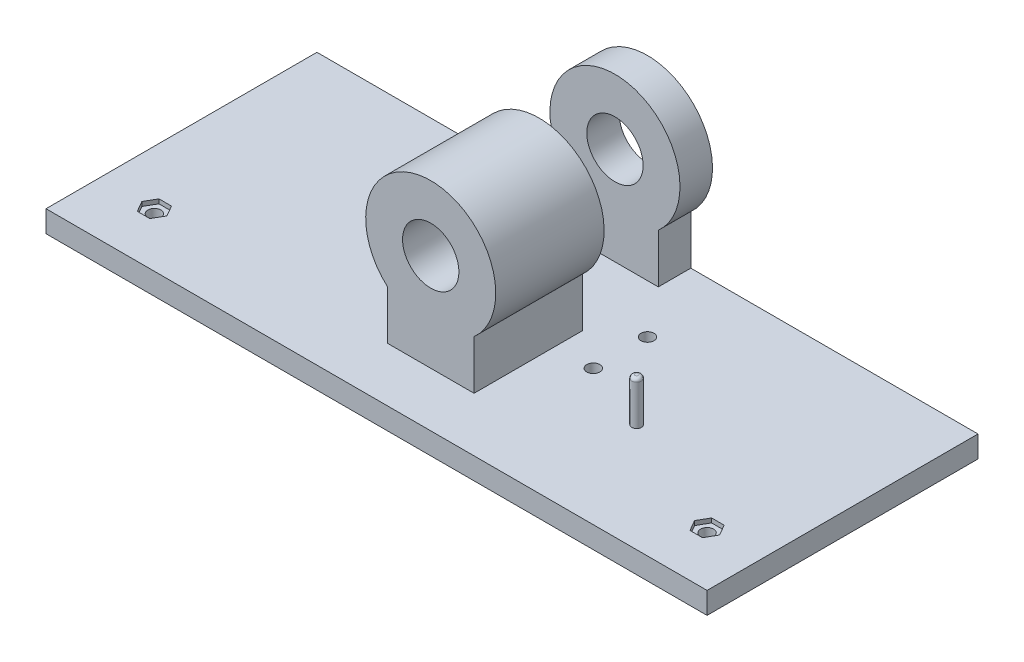
SolidWorks part; units mm, degrees
ref_plane "Front Plane" through (0, 0, 0) normal (0, 0, 1) x (1, 0, 0)
ref_plane "Top Plane" through (0, 0, 0) normal (0, 1, 0) x (1, 0, 0)
ref_plane "Right Plane" through (0, 0, 0) normal (1, 0, 0) x (0, 0, -1)
sketch "Sketch1" plane through (0, 0, 0) normal (0, 1, 0) x (1, 0, 0)
  line L0 (152.5, 125) -> (152.5, 0) construction
  line L1 (0, 0) -> (305, 0)
  line L2 (0, 0) -> (0, 125)
  line L3 (0, 125) -> (305, 125)
  line L4 (305, 0) -> (305, 125)
  line L5 (25, 100) -> (280, 100) construction
  line L6 (280, 25) -> (280, 100) construction
  line L7 (25, 25) -> (280, 25) construction
  line L8 (25, 25) -> (25, 100) construction
  line L9 (152.5, 62.5) -> (25, 62.5) construction
  line L10 (30.7735, 100) -> (27.8868, 105) construction
  line L11 (27.8868, 105) -> (22.1132, 105) construction
  line L12 (22.1132, 105) -> (19.2265, 100) construction
  line L13 (19.2265, 100) -> (22.1132, 95) construction
  line L14 (22.1132, 95) -> (27.8868, 95) construction
  line L15 (27.8868, 95) -> (30.7735, 100) construction
  line L16 (27.8868, 30) -> (30.7735, 25) construction
  line L17 (22.1132, 30) -> (27.8868, 30) construction
  line L18 (19.2265, 25) -> (22.1132, 30) construction
  line L19 (22.1132, 20) -> (19.2265, 25) construction
  line L20 (27.8868, 20) -> (22.1132, 20) construction
  line L21 (30.7735, 25) -> (27.8868, 20) construction
  line L22 (282.8868, 30) -> (277.1132, 30) construction
  line L23 (285.7735, 25) -> (282.8868, 30) construction
  line L24 (282.8868, 20) -> (285.7735, 25) construction
  line L25 (277.1132, 20) -> (282.8868, 20) construction
  line L26 (274.2265, 25) -> (277.1132, 20) construction
  line L27 (277.1132, 30) -> (274.2265, 25) construction
  line L28 (277.1132, 95) -> (274.2265, 100) construction
  line L29 (282.8868, 95) -> (277.1132, 95) construction
  line L30 (285.7735, 100) -> (282.8868, 95) construction
  line L31 (282.8868, 105) -> (285.7735, 100) construction
  line L32 (277.1132, 105) -> (282.8868, 105) construction
  line L33 (274.2265, 100) -> (277.1132, 105) construction
  line L34 (172.5, 75) -> (172.5, 125) construction
  line L35 (132.5, 0) -> (172.5, 0) construction
  line L36 (132.5, 0) -> (132.5, 125) construction
  line L37 (132.5, 125) -> (172.5, 125) construction
  line L38 (172.5, 0) -> (172.5, 125) construction
  line L39 (132.5, 75) -> (172.5, 75) construction
  line L40 (132.5, 75) -> (132.5, 25) construction
  line L41 (132.5, 25) -> (172.5, 25) construction
  line L42 (172.5, 75) -> (172.5, 25) construction
  line L43 (172.5, 75) -> (190, 62.5) construction
  line L48 (190, 62.5) -> (190, 75) construction
  line L49 (190, 75) -> (172.5, 75) construction
  line L50 (190, 62.5) -> (190, 75) construction
  line L51 (190, 75) -> (190, 87.5) construction
  circle A1 centre (25, 100) radius 5 construction
  circle A3 centre (280, 25) radius 3
  circle A4 centre (25, 25) radius 3
  circle A5 centre (190, 62.5) radius 3
  circle A7 centre (190, 87.5) radius 3
  dimension "D3" = 6
  dimension "D7" = 6
  dimension "D1" = 305
  dimension "D2" = 125
  dimension "D5" = 10
  dimension "D6" = 40
  dimension "D8" = 50
  dimension "D9" = 12.5
  dimension "D10" = 17.5
  dimension "D4" = 25
  dimension "D11" = 2
extrude "Boss-Extrude1" add sketch "Sketch1" along normal blind 10
sketch "Sketch6" plane through (0, 10, 0) normal (0, 1, 0) x (1, 0, 0)
  line L0 (152.5, 125) -> (152.5, 0) construction
  line L7 (305, 125) -> (0, 125) construction
  line L8 (0, 0) -> (305, 0) construction
  line L9 (152.5, 62.5) -> (0, 62.5) construction
  line L10 (0, 125) -> (0, 0) construction
  line L29 (27.8868, 30) -> (30.7735, 25)
  line L30 (274.2265, 25) -> (277.1132, 20)
  line L31 (277.1132, 20) -> (282.8868, 20)
  line L32 (282.8868, 20) -> (285.7735, 25)
  line L33 (285.7735, 25) -> (282.8868, 30)
  line L34 (282.8868, 30) -> (277.1132, 30)
  line L35 (277.1132, 30) -> (274.2265, 25)
  line L36 (22.1132, 30) -> (27.8868, 30)
  line L37 (19.2265, 25) -> (22.1132, 30)
  line L38 (22.1132, 20) -> (19.2265, 25)
  line L39 (27.8868, 20) -> (22.1132, 20)
  line L40 (30.7735, 25) -> (27.8868, 20)
  circle A0 centre (280, 25) radius 5 construction
  dimension "D1" = 10
extrude "Cut-Extrude1" cut sketch "Sketch6" against normal blind 2
sketch "Sketch7" plane through (0, 10, 0) normal (0, 1, 0) x (1, 0, 0)
  line L0 (0, 0) -> (305, 0) construction
  line L1 (132.5, 25) -> (172.5, 25)
  line L2 (132.5, 25) -> (132.5, 75)
  line L3 (132.5, 75) -> (172.5, 75)
  line L4 (172.5, 25) -> (172.5, 75)
  line L5 (152.5, 0) -> (152.5, 125) construction
  line L6 (305, 125) -> (0, 125) construction
  line L7 (172.5, 75) -> (172.5, 125) construction
  line L18 (132.5, 110) -> (172.5, 110)
  line L19 (132.5, 110) -> (132.5, 125)
  line L20 (132.5, 125) -> (172.5, 125)
  line L21 (172.5, 110) -> (172.5, 125)
  point P11 (152.5, 75)
  point P20 (152.5, 110)
  dimension "D1" = 40
  dimension "D2" = 50
  dimension "D4" = 15
extrude "Boss-Extrude2" add sketch "Sketch7" along normal blind 22.6393
sketch "Sketch11" plane through (0, 0, -25) normal (0, 0, 1) x (1, 0, 0)
  circle A0 centre (152.5, 55) radius 30
  circle A1 centre (152.5, 55) radius 13
  dimension "D1" = 60
  dimension "D2" = 26
extrude "Boss-Extrude3" add sketch "Sketch11" against normal up to surface (100 mm away) up to face at (152.5, 13.1598, -125)
ref_plane "Plane1" through (0, 0, -62.5) normal (0, 0, 1) x (1, 0, 0)
sketch "Sketch12" plane through (305, 0, 0) normal (1, 0, 0) x (0, 0, -1)
  line L0 (125, 85) -> (25, 85) construction
  line L1 (75, 10) -> (110, 10)
  line L2 (75, 10) -> (75, 85)
  line L3 (75, 85) -> (110, 85)
  line L4 (110, 10) -> (110, 85)
  line L6 (110, 32.6393) -> (110, 10) construction
extrude "Cut-Extrude2" cut sketch "Sketch12" against normal through all
sketch "Sketch13" plane through (0, 10, 0) normal (0, 1, 0) x (1, 0, 0)
  line L0 (222.5, 50) -> (172.5, 50) construction
  line L1 (172.5, 25) -> (172.5, 75) construction
  circle A0 centre (222.5, 50) radius 2.25
  dimension "D1" = 4.5
  dimension "D2" = 50
extrude "Boss-Extrude4" add sketch "Sketch13" along normal blind 20
fillet "Fillet1" radius 1.5 1 edges at (222.5, 30, -47.75)
sketch "Sketch14" plane through (0, 0, 0) normal (0, -1, 0) x (1, 0, 0)
  line L0 (195.7735, -87.5) -> (192.8868, -82.5)
  line L1 (195.7735, -62.5) -> (192.8868, -57.5)
  line L2 (192.8868, -57.5) -> (187.1132, -57.5)
  line L3 (187.1132, -57.5) -> (184.2265, -62.5)
  line L4 (184.2265, -62.5) -> (187.1132, -67.5)
  line L5 (187.1132, -67.5) -> (192.8868, -67.5)
  line L6 (192.8868, -67.5) -> (195.7735, -62.5)
  line L7 (192.8868, -82.5) -> (187.1132, -82.5)
  line L8 (187.1132, -82.5) -> (184.2265, -87.5)
  line L9 (184.2265, -87.5) -> (187.1132, -92.5)
  line L10 (187.1132, -92.5) -> (192.8868, -92.5)
  line L11 (192.8868, -92.5) -> (195.7735, -87.5)
  circle A0 centre (190, -62.5) radius 5 construction
  dimension "D1" = 10
  dimension "D3" = 15
  dimension "D2" = 2
extrude "Cut-Extrude3" cut sketch "Sketch14" against normal blind 4
equation "\"joint_width\"=4"
equation "\"D2@Sketch7\"=5"
equation "\"short_base_length\"=12.5"
equation "\"D2@Sketch1\"=\"short_base_length\""
equation "\"outer_diam_main_joint\"=6"
equation "\"D1@Sketch11\"=\"outer_diam_main_joint\""
equation "\"D1@Sketch7\"=\"outer_diam_main_joint\"-2"
equation "\"D1@Boss-Extrude2\"=(\"outer_diam_main_joint\"/2)+1.5cm-sqr((\"outer_diam_main_joint\"/2)^2-((\"outer_diam_main_joint\"-2)/2)^2)"
equation "\"D6@Sketch1\"=\"outer_diam_main_joint\"-2"
equation "\"pulleyside\"=1.5"
